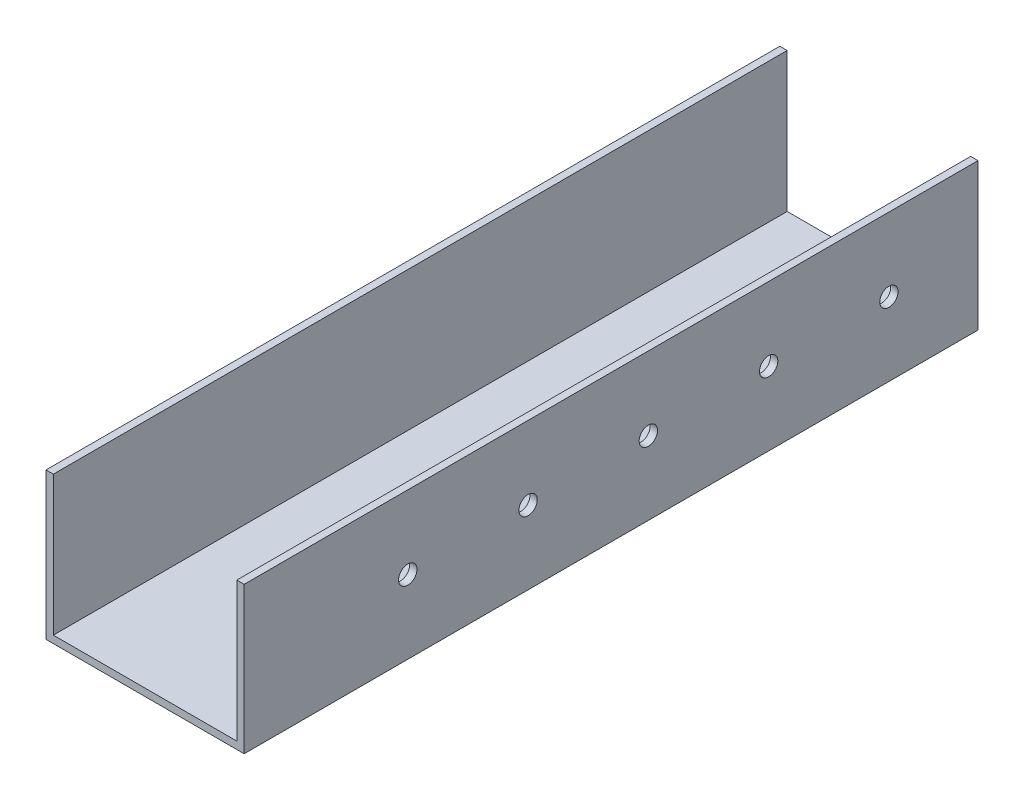
SolidWorks part; units mm, degrees
ref_plane "Alzado" through (0, 0, 0) normal (0, 0, 1) x (1, 0, 0)
ref_plane "Planta" through (0, 0, 0) normal (0, 1, 0) x (1, 0, 0)
ref_plane "Vista lateral" through (0, 0, 0) normal (1, 0, 0) x (0, 0, -1)
sketch "Croquis1" plane through (0, 0, 0) normal (0, 0, 1) x (1, 0, 0)
  line L0 (0, 22.9641) -> (0, -26.2672) construction
  line L1 (-27, -20) -> (27, -20) construction
  line L2 (-27, -20) -> (-27, 20) construction
  line L3 (-27, 20) -> (27, 20) construction
  line L4 (27, -20) -> (27, 20) construction
  line L5 (-27, -20) -> (27, 20) construction
  line L6 (-27, 20) -> (27, -20) construction
  line L7 (-27, 20) -> (-27, -20)
  line L8 (-27, -20) -> (27, -20)
  line L9 (0, -20) -> (0, -18)
  line L10 (25, -18) -> (-25, -18)
  line L11 (-25, -18) -> (-25, 20)
  line L12 (-25, 20) -> (-27, 20)
  line L13 (25, -18) -> (25, 20)
  line L14 (27, 20) -> (27, -20)
  line L15 (25, 20) -> (27, 20)
  point P0 (0, 0)
  dimension "D1" = 40
  dimension "D2" = 54
  dimension "D3" = 2
  dimension "D4" = 2
extrude "Saliente-Extruir1" add sketch "Croquis1" along normal mid plane 200 contours L11 L12 L7 L8 L9 L10 | L10 L11 L12 L7 L8 L14 L15 L13 region at (-26, 19.5174, 0)
sketch "Croquis2" plane through (27, 0, 0) normal (1, 0, 0) x (0, 0, -1)
  line L0 (0, 0) -> (-56.8754, 0) construction
  line L1 (10.16, 0) -> (86.0635, 0) construction
  circle A0 centre (-55.4, 0) radius 2.5
  circle A1 centre (-22.62, 0) radius 2.5
  circle A2 centre (10.16, 0) radius 2.5
  circle A3 centre (42.94, 0) radius 2.5
  circle A4 centre (75.72, 0) radius 2.5
  point P13 (75.72, 0)
  point P16 (69.9483, 0)
  point P17 (0, 0)
  dimension "D2" = 5
  dimension "D6" = 32.78
  dimension "D1" = 55.4
  dimension "D3" = 32.78
  dimension "D4" = 32.78
  dimension "D5" = 32.78
extrude "Cortar-Extruir1" cut sketch "Croquis2" against normal blind 10
